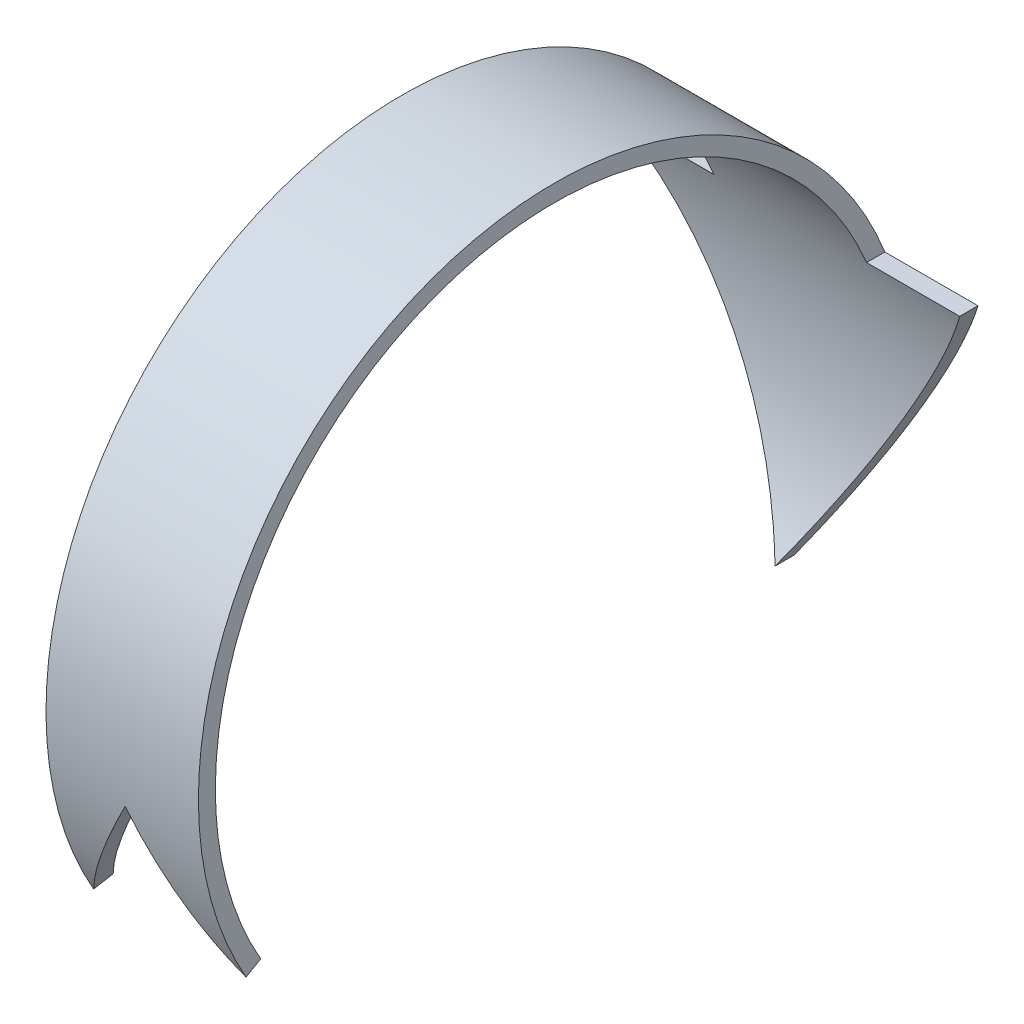
SolidWorks part; units mm, degrees
note: '?' marks a value the reader was unsure of.
ref_plane "SketchPlanes" through (0, 0, 0) normal (0, 0, 1) x (1, 0, 0)
ref_plane "Plane2" through (0, 0, 0) normal (0, 1, 0) x (1, 0, 0)
ref_plane "Symmetry" through (0, 0, 0) normal (1, 0, 0) x (0, 0, -1)
sketch "circularband" plane through (0, 0, 0) normal (0, 0, 1) x (1, 0, 0)
  line L0 (-25, 52.5) -> (25, 52.5)
  line L1 (-25, 52.5) -> (-25, 50)
  line L2 (25, 50) -> (-25, 50)
  line L3 (25, 50) -> (25, 52.5)
  line L4 (0, 0) -> (9.9102, 0) construction
  point P4 (0, 50)
  dimension "headwidth" = 50
  dimension "radius" = 50
  dimension "thickness" = 2.5
revolve "Base-Revolve" add sketch "circularband" angle 120 about L4
ref_axis "arrowaxis" through (-50, 0, 0) along (1, 0, 0)?
sketch "arrowpattern" plane through (0, 0, 0) normal (0, 0, 1) x (1, 0, 0)
  line L0 (-25, 19.3013) -> (25, 19.3013) construction
  line L1 (-25, 19.3013) -> (0, -24) construction
  line L2 (0, -24) -> (25, 19.3013) construction
  line L3 (-11.25, -26.25) -> (-11.25, 13.125) construction
  line L4 (11.25, -26.25) -> (11.25, 13.125) construction
  line L5 (-25, 52.5) -> (-25, -26.25) construction
  line L6 (-11.25, -26.25) -> (0, -6.7644) construction
  line L7 (0, -6.7644) -> (11.25, -26.25) construction
  line L8 (-11.25, 13.125) -> (11.25, 13.125) construction
  line L9 (25, -26.25) -> (25, 52.5) construction
  line L10 (25, -25) -> (-25, -25) construction
  line L13 (-25, -26.25) -> (25, -26.25) construction
  point P11 (0, -25)
  dimension "D1" = 1
  dimension "headangle" = 60
  dimension "tailwidth" = 22.5
sketch "Sketch13" plane through (0, 0, 0) normal (0, 1, 0) x (1, 0, 0)
  line L0 (0, 43.3013) -> (-25, 0) construction
  line L1 (-25, 0) -> (25, 0) construction
  line L2 (-11.25, 0) -> (-11.25, -43.3013) construction
  line L3 (-11.25, -43.3013) -> (0, -23.8157) construction
  line L4 (0, -23.8157) -> (11.25, -43.3013) construction
  line L5 (11.25, -43.3013) -> (11.25, 0) construction
  line L6 (0, 52.5) -> (0, 43.3013) construction
  line L7 (25, 0) -> (0, 43.3013) construction
  line L8 (-11.25, -43.3013) -> (11.25, -43.3013) construction
  line L9 (-25, 0) -> (0, 43.3013)
  line L10 (25, 43.3013) -> (-25, 43.3013) construction
  line L11 (25, -43.3013) -> (-25, -43.3013) construction
  line L12 (25, 52.5) -> (-25, 52.5) construction
  line L14 (0, -23.8157) -> (0, -52.5) construction
  line L15 (-25, -52.5) -> (25, -52.5) construction
  line L16 (0, 43.3013) -> (-25, 0) construction
  line L17 (-25, 0) -> (25, 0) construction
  line L18 (25, 0) -> (0, 43.3013) construction
  line L19 (-11.25, 0) -> (-11.25, -43.3013) construction
  line L20 (-11.25, -43.3013) -> (0, -23.8157) construction
  line L21 (0, -23.8157) -> (11.25, -43.3013) construction
  line L22 (11.25, -43.3013) -> (11.25, 0) construction
  line L23 (0, 43.3013) -> (25, 0)
  line L24 (25, 0) -> (11.25, 0)
  line L25 (11.25, 0) -> (11.25, -43.3013)
  line L26 (11.25, -43.3013) -> (0, -23.8157)
  line L27 (0, -23.8157) -> (-11.25, -43.3013)
  line L28 (-11.25, -43.3013) -> (-11.25, 0)
  line L29 (-11.25, 0) -> (-25, 0)
  line L30 (-12.639, -14.4338) -> (-12.639, 14.4338) construction
  line L31 (-12.639, -14.4338) -> (-12.639, -43.3013) construction
  line L32 (-12.639, 14.4338) -> (-12.639, 43.3013) construction
  point P21 (-12.639, 0)
sketch "Sketch9" plane through (0, 0, 0) normal (0, 0, 1) x (1, 0, 0)
  line L0 (-11.25, 52.5) -> (11.25, 52.5)
  line L1 (11.25, 52.5) -> (11.25, 19.3013)
  line L2 (-25, 19.3013) -> (25, 19.3013) construction
  line L3 (11.25, 19.3013) -> (25, 19.3013)
  line L4 (25, 19.3013) -> (0, -24)
  line L5 (0, -24) -> (-25, 19.3013)
  line L6 (-25, 19.3013) -> (-11.25, 19.3013)
  line L7 (-11.25, 19.3013) -> (-11.25, 52.5)
  line L8 (-25, 52.5) -> (25, 52.5) construction
  line L9 (0, 50) -> (0, 52.5) construction
  line L10 (-11.25, -26.25) -> (-11.25, 13.125) construction
extrude "head1" cut sketch "Sketch9" against normal through all flip side to cut
sketch "Sketch10" plane through (0, 0, 0) normal (0, 0, 1) x (1, 0, 0)
  line L0 (-25, 52.5) -> (25, 52.5) construction
  line L1 (0, -6.7644) -> (11.25, -26.25)
  line L2 (11.25, -26.25) -> (11.25, 52.5)
  line L3 (11.25, 52.5) -> (-11.25, 52.5)
  line L4 (-11.25, 52.5) -> (-11.25, -26.25)
  line L5 (0, -6.7644) -> (-11.25, -26.25)
  line L6 (0, 50) -> (0, 52.5) construction
extrude "tail1" cut sketch "Sketch10" along normal through all flip side to cut
sketch "Sketch11" plane through (0, 0, 0) normal (0, 0, 1) x (1, 0, 0)
  line L0 (-11.25, 13.125) -> (11.25, 13.125)
  line L1 (11.25, 13.125) -> (11.25, 19.3013)
  line L2 (-25, 19.3013) -> (25, 19.3013) construction
  line L3 (11.25, 19.3013) -> (25, 19.3013)
  line L4 (25, 19.3013) -> (0, -24)
  line L5 (0, -24) -> (-25, 19.3013)
  line L6 (-25, 19.3013) -> (-11.25, 19.3013)
  line L7 (-11.25, 19.3013) -> (-11.25, 13.125)
extrude "head2" [suppressed] cut sketch "Sketch11" along normal through all flip side to cut
sketch "Sketch12" plane through (0, 0, 0) normal (0, 0, 1) x (1, 0, 0)
  line L0 (-11.25, 13.125) -> (11.25, 13.125)
  line L1 (11.25, 13.125) -> (11.25, -26.25)
  line L2 (11.25, -26.25) -> (0, -6.7644)
  line L3 (0, -6.7644) -> (-11.25, -26.25)
  line L4 (-11.25, -26.25) -> (-11.25, 13.125)
extrude "tail2" [suppressed] cut sketch "Sketch12" against normal through all flip side to cut
extrude "Cut-Extrude1" [suppressed] cut sketch "Sketch13" against normal through all and the other way through all flip side to cut
